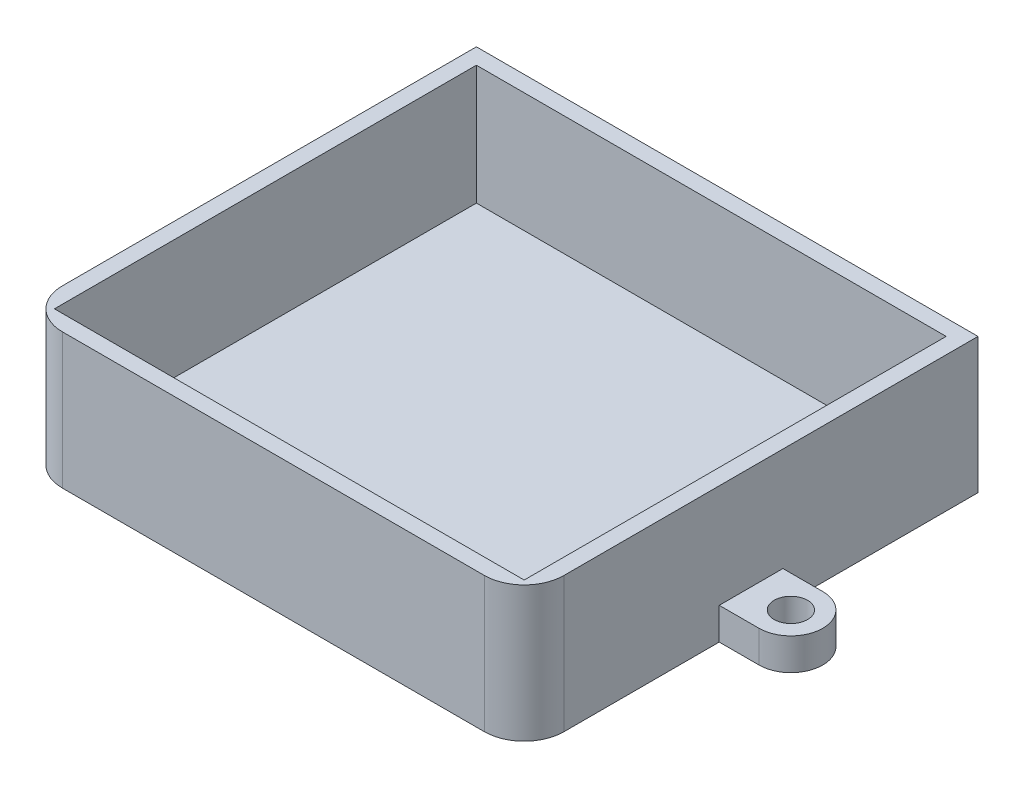
SolidWorks part; units mm, degrees
ref_plane "Front Plane" through (0, 0, 0) normal (0, 0, 1) x (1, 0, 0)
ref_plane "Top Plane" through (0, 0, 0) normal (0, 1, 0) x (1, 0, 0)
ref_plane "Right Plane" through (0, 0, 0) normal (1, 0, 0) x (0, 0, -1)
sketch "Sketch1" plane through (0, 0, 0) normal (0, 1, 0) x (1, 0, 0)
  line L1 (-29.5, 26.5) -> (29.5, 26.5)
  line L2 (-29.5, 26.5) -> (-29.5, -26.5)
  line L3 (-29.5, -26.5) -> (29.5, -26.5)
  line L4 (29.5, 26.5) -> (29.5, -26.5)
  line L5 (-29.5, 26.5) -> (29.5, -26.5) construction
  line L6 (-29.5, -26.5) -> (29.5, 26.5) construction
  line L7 (-31.5, 28.5) -> (31.5, 28.5)
  line L8 (-31.5, 28.5) -> (-31.5, -28.5)
  line L9 (-31.5, -28.5) -> (31.5, -28.5)
  line L10 (31.5, 28.5) -> (31.5, -28.5)
  line L11 (-31.5, 28.5) -> (31.5, -28.5) construction
  line L12 (-31.5, -28.5) -> (31.5, 28.5) construction
  point P0 (0, 0)
  point P6 (0, 0)
  dimension "D1" = 59
  dimension "D2" = 2
  dimension "D3" = 2
  dimension "D4" = 53
extrude "Boss-Extrude1" add sketch "Sketch1" along normal blind 15
sketch "Sketch2" plane through (0, 0, 0) normal (0, -1, 0) x (1, 0, 0)
  line L1 (-31.5, 28.5) -> (31.5, 28.5)
  line L2 (-31.5, 28.5) -> (-31.5, -28.5)
  line L3 (-31.5, -28.5) -> (31.5, -28.5)
  line L4 (31.5, 28.5) -> (31.5, -28.5)
extrude "Boss-Extrude2" add sketch "Sketch2" along normal blind 2
ref_plane "Plane1" through (0, 0, 0) normal (-1, 0, 0) x (0, 0, 1)
sketch "Sketch4" plane through (0, -2, 0) normal (0, -1, 0) x (1, 0, 0)
  line L0 (-31.5, 0) -> (31.5, 0) construction
  line L1 (-31.5, 28.5) -> (-31.5, -28.5) construction
  line L2 (31.5, -28.5) -> (31.5, 28.5) construction
  line L3 (-36.5, 4) -> (-31.5, 4)
  line L4 (-31.5, 4) -> (-31.5, -4)
  line L5 (-31.5, -4) -> (-36.5, -4)
  arc A1 (-36.5, 4) -> (-36.5, -4) centre (-36.5, 0) ccw
  point P7 (-31.5, 0)
  point P12 (0, 0)
  dimension "D1" = 8
  dimension "D2" = 5
extrude "Boss-Extrude3" add sketch "Sketch4" against normal blind 4
sketch "Sketch5" plane through (0, 2, 0) normal (0, 1, 0) x (1, 0, 0)
  circle A0 centre (-36.5, 0) radius 2.1
  dimension "D1" = 4.2
extrude "Cut-Extrude1" cut sketch "Sketch5" against normal up to surface (4 mm away) up to face at (-17.5, -2, 0)
mirror "Mirror1" about plane through (0, 0, 0) normal (-1, 0, 0) of "Cut-Extrude1", "Boss-Extrude3"
fillet "Fillet1" radius 5 2 edges at (-31.5, 6.5, 28.5) (31.5, 6.5, 28.5)
